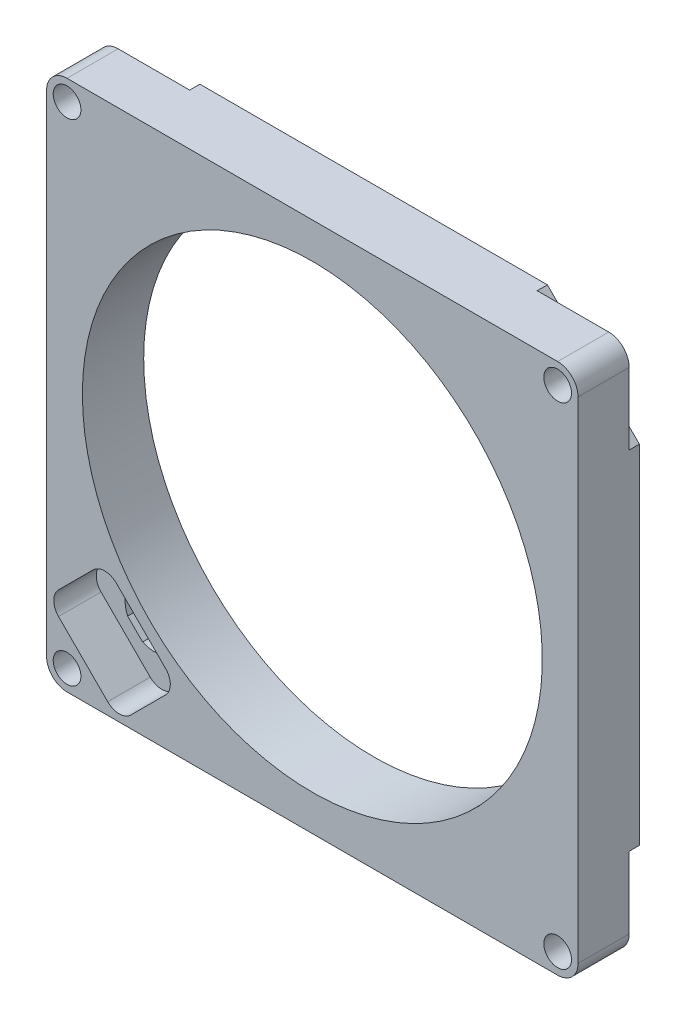
SolidWorks part; units mm, degrees
material "PET"
ref_plane "Front Plane" through (0, 0, 0) normal (0, 0, 1) x (1, 0, 0)
ref_plane "Top Plane" through (0, 0, 0) normal (0, 1, 0) x (1, 0, 0)
ref_plane "Right Plane" through (0, 0, 0) normal (1, 0, 0) x (0, 0, -1)
sketch "Sketch1" plane through (0, 0, 0) normal (0, 0, 1) x (1, 0, 0)
  line L8 (-213.995, 2363.8407) -> (-213.995, 2440.0407)
  line L9 (-217.17, 2443.2157) -> (-293.37, 2443.2157)
  line L10 (-296.545, 2440.0407) -> (-296.545, 2363.8407)
  line L11 (-293.37, 2360.6657) -> (-217.17, 2360.6657)
  arc A8 (-217.17, 2360.6657) -> (-213.995, 2363.8407) centre (-217.17, 2363.8407) ccw
  arc A9 (-213.995, 2440.0407) -> (-217.17, 2443.2157) centre (-217.17, 2440.0407) ccw
  arc A10 (-293.37, 2443.2157) -> (-296.545, 2440.0407) centre (-293.37, 2440.0407) ccw
  arc A11 (-296.545, 2363.8407) -> (-293.37, 2360.6657) centre (-293.37, 2363.8407) ccw
extrude "Boss-Extrude1" add sketch "Sketch1" against normal up to surface (7.9375 mm away)
sketch "Sketch2" plane through (0, 0, -7.9375) normal (0, 0, -1) x (-1, 0, 0)
  line L16 (282.2575, 2360.6657) -> (296.545, 2374.9532)
  line L17 (296.545, 2374.9532) -> (296.545, 2428.9282)
  line L18 (296.545, 2428.9282) -> (282.2575, 2443.2157)
  line L19 (282.2575, 2443.2157) -> (228.2825, 2443.2157)
  line L20 (228.2825, 2443.2157) -> (213.995, 2428.9282)
  line L21 (213.995, 2428.9282) -> (213.995, 2374.9532)
  line L22 (213.995, 2374.9532) -> (228.2825, 2360.6657)
  line L23 (228.2825, 2360.6657) -> (282.2575, 2360.6657)
  circle A1 centre (255.27, 2401.9407) radius 35.7188
extrude "Boss-Extrude2" add sketch "Sketch2" along normal blind 1.5875
sketch "Sketch3" plane through (0, 0, -7.9375) normal (0, 0, -1) x (-1, 0, 0)
  circle A1 centre (255.27, 2401.9407) radius 35.7188
  circle A2 centre (255.27, 2401.9407) radius 35.7188
  dimension "D1" = 0
extrude "Cut-Extrude1" cut sketch "Sketch3" against normal through all and the other way through all
hole_wizard "#6 Clearance Hole1" positions "Sketch5" profile "Sketch4" hole size "#6" standard "ANSI Inch" end condition through all
sketch "Sketch5" plane through (0, 0, -7.9375) normal (0, 0, -1) x (-1, 0, 0)
  point P0 (217.17, 2440.0407)
  point P2 (293.37, 2440.0407)
  point P4 (293.37, 2363.8407)
  point P6 (217.17, 2363.8407)
sketch "Sketch4" plane through (-217.17, 2440.0407, -7.9375) normal (1, 0, 0) x (0, 1, 0)
  line L0 (0, 0) -> (0, 7.9375)
  line L1 (0, 7.9375) -> (2.1526, 7.9375)
  line L2 (2.1526, 7.9375) -> (2.1526, 0)
  line L5 (2.1526, 0) -> (0, 0)
  line L11 (0, -6.35) -> (0, 107.95) construction
  dimension "Thru Hole Dia." = 4.3053
  dimension "Thru Hole Depth" = 7.9375
sketch "Sketch6" plane through (0, 0, 0) normal (0, 0, 1) x (1, 0, 0)
  line L0 (-287.0585, 2362.519) -> (-294.6917, 2370.1522)
  line L1 (-283.4664, 2362.519) -> (-278.0783, 2367.9071)
  line L2 (-294.6917, 2373.7443) -> (-289.3036, 2379.1325)
  line L3 (-278.0783, 2371.4992) -> (-285.7115, 2379.1325)
  line L4 (-285.2625, 2360.7229) -> (-287.5075, 2380.9285) construction
  line L5 (-296.4878, 2371.9483) -> (-276.2822, 2369.7032) construction
  arc A0 (-294.6917, 2370.1522) -> (-294.6917, 2373.7443) centre (-292.8957, 2371.9483) cw
  arc A1 (-283.4664, 2362.519) -> (-287.0585, 2362.519) centre (-285.2625, 2364.315) cw
  arc A2 (-278.0783, 2367.9071) -> (-278.0783, 2371.4992) centre (-279.8743, 2369.7032) ccw
  arc A3 (-289.3036, 2379.1325) -> (-285.7115, 2379.1325) centre (-287.5075, 2377.3364) cw
  point P1 (-286.385, 2370.8257)
  dimension "D3" = 2.54
  dimension "D1" = 12.7
  dimension "D2" = 15.875
extrude "Cut-Extrude2" cut sketch "Sketch6" against normal offset from surface (6.604 mm away) 2.921 up to face at (-255.27, 2401.9407, -9.525)
hole_wizard "5/16 Clearance Hole1" positions "Sketch8" profile "Sketch7" hole size "5/16" standard "ANSI Inch" end condition through all
sketch "Sketch8" plane through (0, 0, -9.525) normal (0, 0, -1) x (-1, 0, 0)
  point P0 (286.385, 2370.8257)
sketch "Sketch7" plane through (-286.385, 2370.8257, -9.525) normal (1, 0, 0) x (0, 1, 0)
  line L0 (0, 0) -> (0, 9.525)
  line L1 (0, 9.525) -> (4.1021, 9.525)
  line L2 (4.1021, 9.525) -> (4.1021, 0)
  line L5 (4.1021, 0) -> (0, 0)
  line L11 (0, -6.35) -> (0, 107.95) construction
  dimension "Thru Hole Dia." = 8.2042
  dimension "Thru Hole Depth" = 9.525
sketch "Sketch9" plane through (0, 0, -9.525) normal (0, 0, -1) x (-1, 0, 0)
  circle A0 centre (286.385, 2370.8257) radius 4.572
  dimension "D1" = 9.144
extrude "Cut-Extrude3" cut sketch "Sketch9" against normal through all
sketch "Sketch10" plane through (0, 0, -7.9375) normal (0, 0, -1) x (-1, 0, 0)
  line L0 (288.2377, 2366.6459) -> (290.5648, 2368.973)
  arc A0 (288.2377, 2366.6459) -> (290.5648, 2368.973) centre (286.385, 2370.8257) ccw construction
  arc A1 (288.2377, 2366.6459) -> (290.5648, 2368.973) centre (286.385, 2370.8257) ccw
extrude "Boss-Extrude3" add sketch "Sketch10" against normal up to surface (1.3335 mm away) up to face at (-290.957, 2370.8257, -6.604)
pattern_circular "CirPattern1" count 4 over 360 about axis through (-286.385, 2370.8257, 0) along (0, 0, -1) of "Boss-Extrude3"
sketch "Sketch11" plane through (0, 0, -7.9375) normal (0, 0, -1) x (-1, 0, 0)
  line L0 (282.2052, 2372.6784) -> (284.5323, 2375.0055) construction
  line L1 (288.2377, 2375.0055) -> (290.5648, 2372.6784) construction
  line L2 (284.5323, 2366.6459) -> (282.2052, 2368.973) construction
  line L3 (282.2052, 2372.6784) -> (284.5323, 2375.0055)
  line L4 (288.2377, 2375.0055) -> (290.5648, 2372.6784)
  line L5 (284.5323, 2366.6459) -> (282.2052, 2368.973)
  arc A0 (284.5323, 2375.0055) -> (282.2052, 2372.6784) centre (286.385, 2370.8257) ccw construction
  arc A1 (290.5648, 2372.6784) -> (288.2377, 2375.0055) centre (286.385, 2370.8257) ccw construction
  arc A2 (282.2052, 2368.973) -> (284.5323, 2366.6459) centre (286.385, 2370.8257) ccw construction
  arc A3 (284.5323, 2375.0055) -> (282.2052, 2372.6784) centre (286.385, 2370.8257) ccw
  arc A4 (290.5648, 2372.6784) -> (288.2377, 2375.0055) centre (286.385, 2370.8257) ccw
  arc A5 (282.2052, 2368.973) -> (284.5323, 2366.6459) centre (286.385, 2370.8257) ccw
extrude "Boss-Extrude4" add sketch "Sketch11" along normal up to surface (1.5875 mm away) up to face at (-261.4713, 2395.7394, -9.525)
